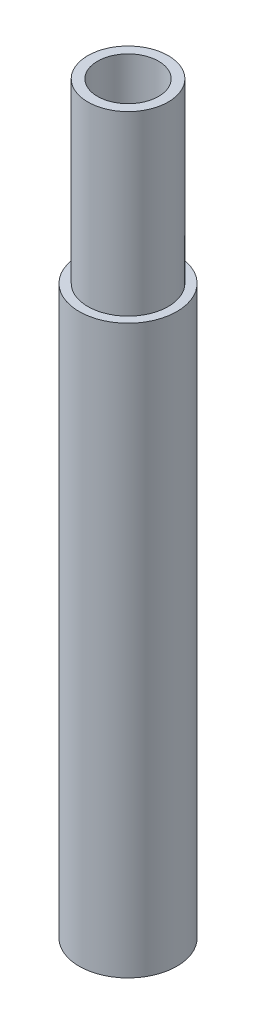
SolidWorks part; units mm, degrees
material "PP Copolymer"
ref_plane "Front Plane" through (0, 0, 0) normal (0, 0, 1) x (1, 0, 0)
ref_plane "Top Plane" through (0, 0, 0) normal (0, 1, 0) x (1, 0, 0)
ref_plane "Right Plane" through (0, 0, 0) normal (1, 0, 0) x (0, 0, -1)
ref_axis "X-axis" through (-88.99, 0, 0) along (1, 0, 0)
ref_axis "Y-axis" through (0, 55, 0) along (0, -1, 0)
ref_axis "Z-axis" through (0, 0, -88.99) along (0, 0, 1)
sketch "Sketch1" plane through (0, 0, 0) normal (0, 0, 1) x (1, 0, 0)
  line L0 (0, 0) -> (0, 77) construction
  line L1 (-5.055, 0) -> (-5.055, 58.67)
  line L2 (-5.055, 58.67) -> (-4.16, 58.67)
  line L3 (-4.16, 58.67) -> (-4.16, 77)
  line L4 (-4.16, 77) -> (-3.16, 77)
  line L5 (-3.16, 77) -> (-3.16, 57.67)
  line L6 (-3.16, 57.67) -> (-4.055, 57.67)
  line L7 (-4.055, 57.67) -> (-4.055, 0)
  line L8 (-4.055, 0) -> (-5.055, 0)
  point P5 (0, 0)
  point P12 (0, 0)
  point P13 (0, 0)
  point P14 (0, 0)
  point P15 (0, 0)
  dimension "D1" = 77
  dimension "D2" = 6.32
  dimension "D3" = 10.11
  dimension "D4" = 1
  dimension "D5" = 1
  dimension "D7" = 1
  dimension "D8" = 58.67
  dimension "D9" = 57.67
revolve "Revolve1" add sketch "Sketch1" angle 360 about L0
thread "Thread1" pitch 0.7056 method extrude profile "Thread Profile1" start angle 0, offset 0, length 13.47, pitch 0.7056, diameter 8.11
ref_plane "Plane1" through (4.055, 0, 0) normal (0, 0, 1) x (1, 0, 0)
sketch "Thread Profile1" plane through (4.055, 0, 0) normal (0, 0, 1) x (1, 0, 0)
  line L0 (0, 0) -> (0, 0.7056) construction
  line L11 (0, 0) -> (0, 0.6174)
  line L12 (0, 0.6174) -> (-0.3819, 0.3969)
  line L13 (-0.3819, 0.3969) -> (-0.3819, 0.2205)
  line L15 (-0.3819, 0.2205) -> (0, 0)
  line L17 (-0.3819, 0.3087) -> (0, 0.3087) construction
  point P2 (0, 0)
  dimension "Pitch" = 0.7056
  dimension "Profile_Angle" = 60
  dimension "Profile_Land" = 0.1764
  dimension "Profile_Height" = 0.3819
